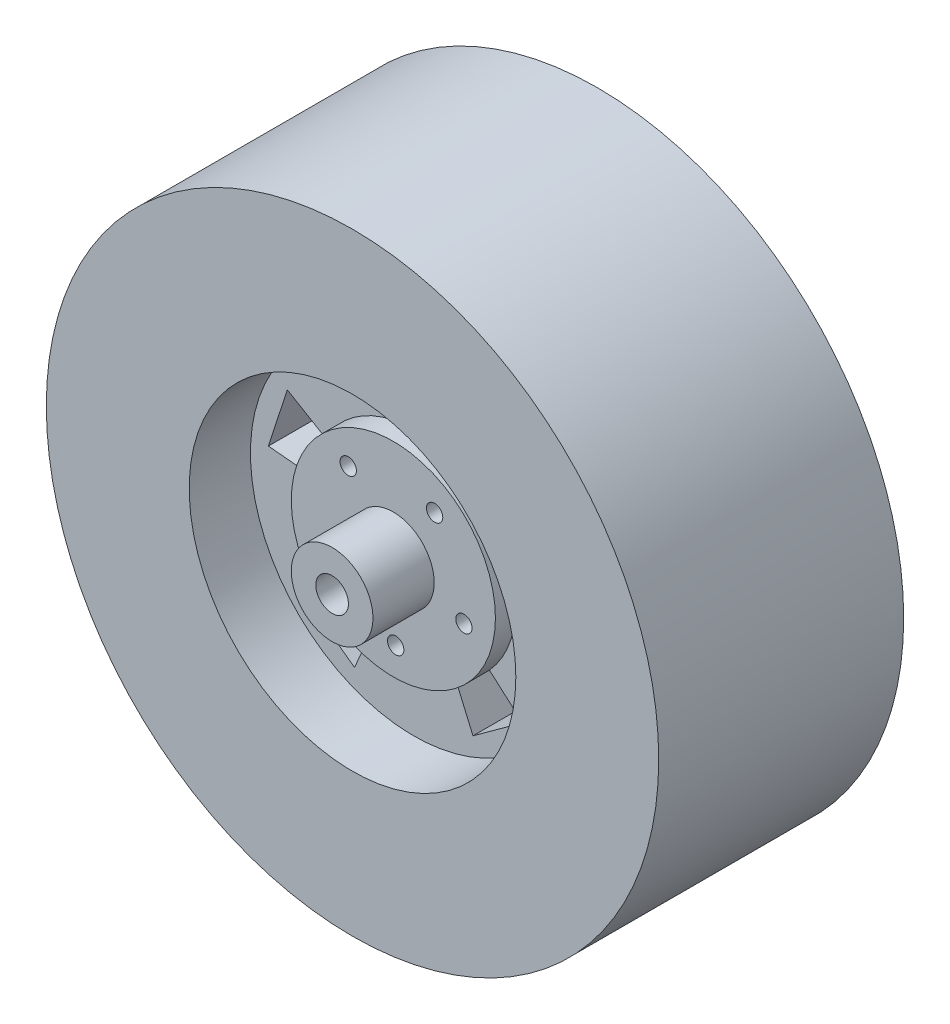
SolidWorks part; units mm, degrees
ref_plane "Front Plane" through (0, 0, 0) normal (0, 0, 1) x (1, 0, 0)
ref_plane "Top Plane" through (0, 0, 0) normal (0, 1, 0) x (1, 0, 0)
ref_plane "Right Plane" through (0, 0, 0) normal (1, 0, 0) x (0, 0, -1)
sketch "Sketch1" plane through (0, 0, 0) normal (0, 0, 1) x (1, 0, 0)
  circle A0 centre (0, 0) radius 75
  circle A1 centre (0, 0) radius 40
  dimension "D1" = 150
  dimension "D2" = 80
extrude "Boss-Extrude1" add sketch "Sketch1" along normal blind 60
sketch "Sketch2" plane through (0, 0, 0) normal (0, 0, 1) x (1, 0, 0)
  line L0 (0, 40) -> (0, 10) construction
  line L1 (7.5, 35) -> (-7.5, 35)
  line L2 (3, 15) -> (-3, 15)
  line L3 (7.5, 35) -> (3, 15)
  line L4 (-7.5, 35) -> (-3, 15)
  line L5 (30.9694, 17.9485) -> (13.3388, 7.4884)
  line L6 (35.6046, 3.6827) -> (30.9694, 17.9485)
  line L7 (35.6046, 3.6827) -> (15.1929, 1.7821)
  line L8 (15.1929, 1.7821) -> (13.3388, 7.4884)
  line L9 (26.6401, -23.9072) -> (11.2438, -10.3719)
  line L10 (14.5049, -32.724) -> (26.6401, -23.9072)
  line L11 (14.5049, -32.724) -> (6.3897, -13.8986)
  line L12 (6.3897, -13.8986) -> (11.2438, -10.3719)
  line L13 (-14.5049, -32.724) -> (-6.3897, -13.8986)
  line L14 (-26.6401, -23.9072) -> (-14.5049, -32.724)
  line L15 (-26.6401, -23.9072) -> (-11.2438, -10.3719)
  line L16 (-11.2438, -10.3719) -> (-6.3897, -13.8986)
  line L17 (-35.6046, 3.6827) -> (-15.1929, 1.7821)
  line L18 (-30.9694, 17.9485) -> (-35.6046, 3.6827)
  line L19 (-30.9694, 17.9485) -> (-13.3388, 7.4884)
  line L20 (-13.3388, 7.4884) -> (-15.1929, 1.7821)
  circle A0 centre (0, 0) radius 40
  circle A1 centre (0, 0) radius 10
  point P9 (0, 35)
  point P12 (0, 15)
  point P30 (0, 0)
  dimension "D1" = 80
  dimension "D2" = 20
  dimension "D3" = 15
  dimension "D4" = 35
  dimension "D5" = 6
  dimension "D6" = 15
  dimension "D7" = 5
extrude "Boss-Extrude2" add sketch "Sketch2" along normal blind 15 and the other way blind 15 from offset 30
sketch "Sketch5" plane through (0, 0, 45) normal (0, 0, 1) x (1, 0, 0)
  circle A0 centre (0, 0) radius 25
  circle A1 centre (-11.0409, 14.2161) radius 2
  circle A2 centre (10.1085, 14.8935) radius 2
  circle A3 centre (17.2883, -5.0114) radius 2
  circle A4 centre (0.5762, -17.9908) radius 2
  circle A5 centre (-16.9322, -6.1075) radius 2
  circle A6 centre (0, 0) radius 4
  point P16 (0, 0)
  dimension "D1" = 50
  dimension "D2" = 4
  dimension "D3" = 18
  dimension "D5" = 8
  dimension "D4" = 5
extrude "Boss-Extrude4" add sketch "Sketch5" along normal blind 5
extrude "Boss-Extrude5" add sketch "Sketch5<2>" against normal blind 5 from offset 30 offset against normal yes
sketch "Sketch5<2>" plane through (0, 0, 45) normal (0, 0, 1) x (1, 0, 0) same geometry as "Sketch5"
sketch "Sketch6" plane through (0, 0, 10) normal (0, 0, -1) x (-1, 0, 0)
  circle A0 centre (0, 0) radius 10
  circle A2 centre (0, 0) radius 4
  dimension "D1" = 20
  dimension "D2" = 8
extrude "Boss-Extrude6" add sketch "Sketch6" along normal blind 15
extrude "Boss-Extrude7" add sketch "Sketch6<2>" against normal blind 15 from offset 40 offset against normal yes
sketch "Sketch6<2>" plane through (0, 0, 10) normal (0, 0, -1) x (-1, 0, 0) same geometry as "Sketch6"
